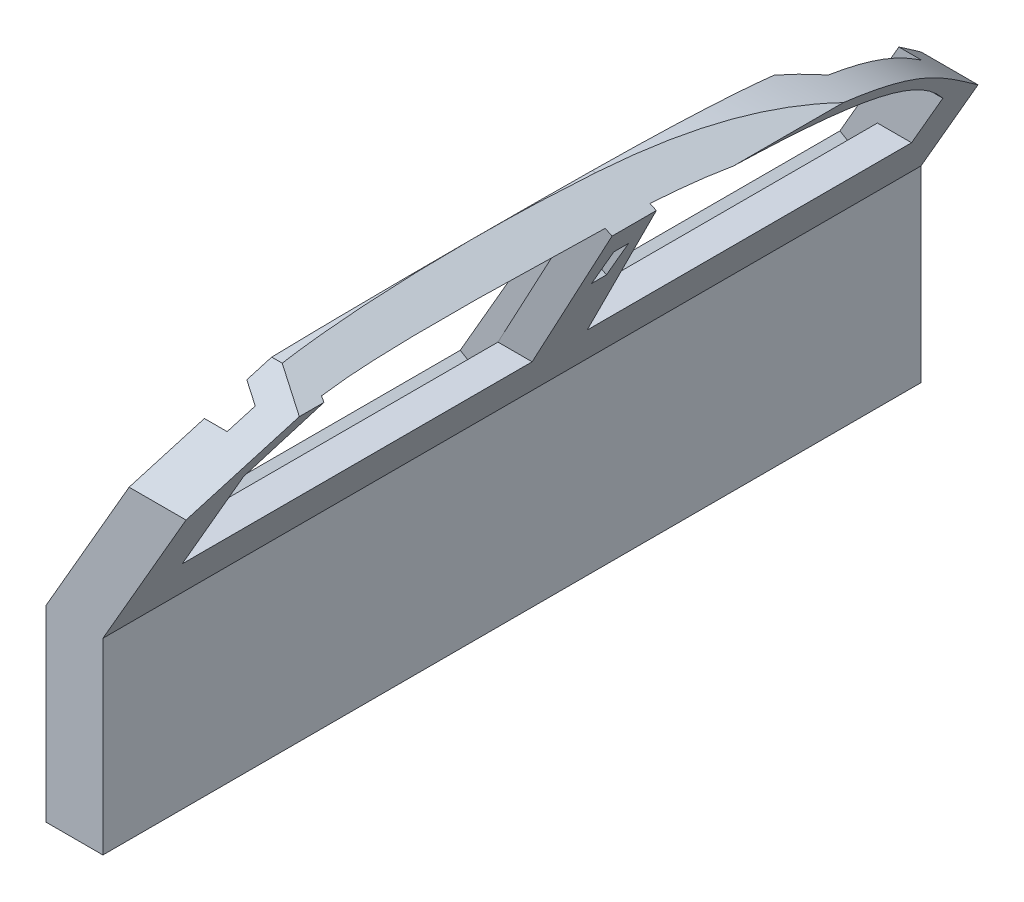
SolidWorks part; units mm, degrees
note: The reader was unsure of these and kept them because the rebuilt part matched: shared geometry of "스케치4<3>".
ref_plane "정면" through (0, 0, 0) normal (0, 0, 1) x (1, 0, 0)
ref_plane "윗면" through (0, 0, 0) normal (0, 1, 0) x (1, 0, 0)
ref_plane "우측면" through (0, 0, 0) normal (1, 0, 0) x (0, 0, -1)
sketch "스케치1" plane through (0, 0, 0) normal (1, 0, 0) x (0, 0, -1)
  line L0 (-3.3731, 1.3955) -> (806.6253, -0.2335) construction
  line L3 (-41.993, -303.6191) -> (788.007, -303.6191)
  line L4 (788.007, -303.6191) -> (788.007, -12.9055)
  line L5 (45.3257, 132.1987) -> (-41.993, 32.8929)
  line L6 (-41.993, 32.8929) -> (-41.993, -303.6191)
  line L7 (54.4277, 114.3899) -> (4.1166, 54.2146)
  line L8 (4.1166, 54.2146) -> (4.1166, -53.6191)
  line L9 (744.1166, -53.6191) -> (414.9329, -53.6191)
  line L10 (344.322, 115.5992) -> (359.1166, -53.6191)
  line L11 (389.1166, 115.2559) -> (414.9329, -53.6191)
  line L12 (744.1166, -53.6191) -> (744.1166, 1.3809)
  line L13 (359.1166, -53.6191) -> (4.1166, -53.6191)
  spline S0 degree 3 poles (788.007, -12.9055) (680.2615, 78.2543) (631.21, 128.4159) (368.7501, 135.2559) knots 0 0 0 0 1 1 1 1
  spline S1 degree 3 poles (45.3257, 132.1987) (134.9896, 137.2114) (265.4636, 138.0115) (368.7501, 135.2559) knots 0 0 0 0 1 1 1 1
  spline S2 degree 3 poles (54.4277, 114.3899) (135.6083, 118.7507) (305.7634, 115.6463) (389.1166, 115.2559) knots 0 0 0 0 1 1 1 1
  spline S3 degree 3 poles (389.1166, 115.2559) (584.5975, 110.8255) (668.4477, 84.914) (744.1166, 1.3809) knots 0.027736 0.027736 0.027736 0.027736 0.84207 0.84207 0.84207 0.84207
  point P21 (744.1166, -53.6191)
  dimension "D7" = 830
  dimension "D1" = 810
  dimension "D2" = 355
  dimension "D3" = 168.875
  dimension "D4" = 168.0089
  dimension "D5" = 355
  dimension "D6" = 250
  dimension "D8" = 30
  dimension "D9" = 55
  dimension "D10" = 20
  dimension "D11" = 20
extrude "보스-돌출1" add sketch "스케치1" along normal blind 300
sketch "스케치2" plane through (0, 0, 41.993) normal (0, 0, 1) x (1, 0, 0)
  line L0 (239.6553, 136.8213) -> (239.6553, -303.6191) construction
  line L1 (300, 136.8213) -> (0, 136.8213) construction
  line L2 (300, -303.6191) -> (0, -303.6191) construction
  line L3 (239.6553, 136.8213) -> (95.3177, -113.1787)
  line L4 (95.3177, -113.1787) -> (95.3177, -303.6191)
  line L5 (239.6553, 136.8213) -> (282.9566, 111.8213)
  line L6 (282.9566, 111.8213) -> (153.0527, -113.1787)
  line L7 (153.0527, -113.1787) -> (153.0527, -303.6191)
  line L8 (95.3177, -113.1787) -> (141.3288, -113.1787) construction
  line L9 (0, -303.6191) -> (341.3647, -303.6191)
  line L10 (0, -303.6191) -> (0, 251.4574)
  line L11 (0, 251.4574) -> (341.3647, 251.4574)
  line L12 (341.3647, -303.6191) -> (341.3647, 251.4574)
  line M5 (0, 32.8929) -> (0, -303.6191)
  line M6 (0, -303.6191) -> (300, -303.6191)
  line M7 (300, -303.6191) -> (300, 32.8929)
  line M8 (300, 32.8929) -> (0, 32.8929)
  dimension "D1" = 250
  dimension "D2" = 30
  dimension "D3" = 50
extrude "컷-돌출1" cut sketch "스케치2" against normal through all both and the other way through all contours L9 L12 L11 L10 L3 L5 L6 M8 M7 | L4 L3 M8 M5 M6 | L6 L7 M6 M7 M8
sketch "스케치4" plane through (120.4961, -69.5685, 0) normal (-0.866, 0.5, 0) x (0, 0, 1)
  line L0 (-389.1166, 197.9899) -> (-359.1166, 197.9899) construction
  line L2 (-744.1166, 18.4168) -> (-744.1166, 213.4168)
  line L3 (-744.1166, 213.4168) -> (-389.1166, 213.4168)
  line L4 (-389.1166, 17.9899) -> (-389.1166, 213.4168)
  line L6 (-359.1166, 18.4168) -> (-359.1166, 212.9899)
  line L7 (-359.1166, 212.9899) -> (-4.1166, 212.9899)
  line L8 (-4.1166, 17.9899) -> (-4.1166, 212.9899)
  line L9 (-381.6166, 197.9899) -> (-366.6166, 197.9899)
  line L10 (-381.6166, 197.9899) -> (-381.6166, 152.9899)
  line L11 (-381.6166, 152.9899) -> (-366.6166, 152.9899)
  line L12 (-366.6166, 197.9899) -> (-366.6166, 152.9899)
  line L13 (-744.1166, 18.4168) -> (-744.1166, -11.5832)
  line L14 (-744.1166, -11.5832) -> (-389.1166, -11.5832)
  line L15 (-389.1166, -11.5832) -> (-389.1166, 17.9899)
  line L16 (-359.1166, 18.4168) -> (-359.1166, -12.0101)
  line L17 (-359.1166, -12.0101) -> (-4.1166, -12.0101)
  line L18 (-4.1166, -12.0101) -> (-4.1166, 17.9899)
  point P16 (-374.1166, 197.9899)
  point P17 (-374.1166, 197.9899)
  dimension "D1" = 355
  dimension "D2" = 195
  dimension "D3" = 195
  dimension "D4" = 355
  dimension "D5" = 15
  dimension "D6" = 45
  dimension "D7" = 225
  dimension "15" = 15
  dimension "90" = 90
  dimension "225" = 225
extrude "컷-돌출2" cut sketch "스케치4" against normal through all contours L10 L11 L12 L9
extrude "컷-돌출3" cut sketch "스케치4<3>" against normal blind 20
sketch "스케치4<3>" plane through (120.4961, -69.5685, 0) normal (-0.866, 0.5, 0) x (0, 0, 1) same geometry as "스케치4"
